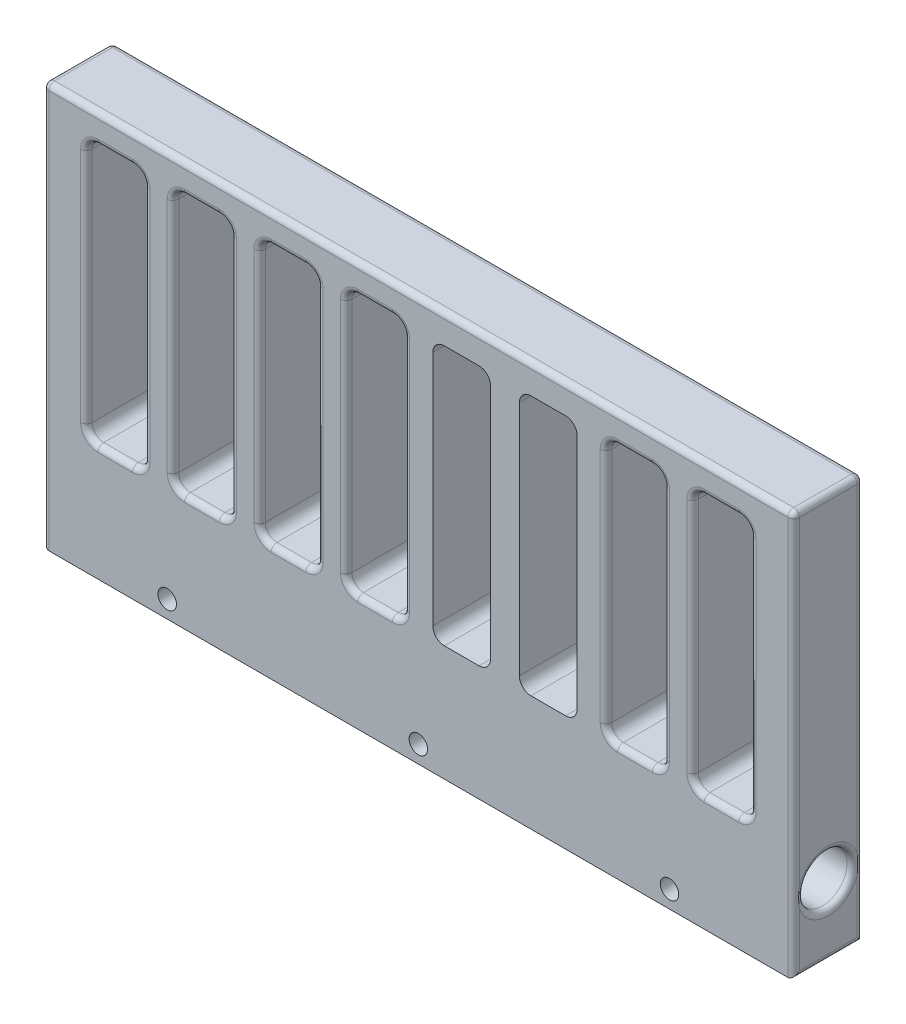
SolidWorks part; units mm, degrees
ref_plane "Plan de face" through (0, 0, 0) normal (0, 0, 1) x (1, 0, 0)
ref_plane "Plan de dessus" through (0, 0, 0) normal (0, 1, 0) x (1, 0, 0)
ref_plane "Plan de droite" through (0, 0, 0) normal (1, 0, 0) x (0, 0, -1)
sketch "Esquisse1" plane through (0, 0, 0) normal (0, 0, 1) x (1, 0, 0)
  line L1 (0, 0) -> (130, 0)
  line L2 (0, 0) -> (0, 70)
  line L3 (0, 70) -> (130, 70)
  line L4 (130, 0) -> (130, 70)
  dimension "D1" = 70
  dimension "D2" = 130
extrude "Boss.-Extru.1" add sketch "Esquisse1" along normal blind 12
sketch "Esquisse2" plane through (0, 0, 12) normal (0, 0, 1) x (1, 0, 0)
  line L31 (0, 20) -> (130, 20) construction
  line L37 (0, 70) -> (0, 0) construction
  line L42 (130, 0) -> (130, 70) construction
  line L47 (0, 0) -> (130, 0) construction
  line L52 (130, 70) -> (0, 70) construction
  line L57 (7.5, 20) -> (17.5, 20)
  line L58 (7.5, 20) -> (7.5, 65)
  line L59 (7.5, 65) -> (17.5, 65)
  line L60 (17.5, 20) -> (17.5, 65)
  line L61 (22.5, 20) -> (22.5, 65)
  line L62 (22.5, 65) -> (32.5, 65)
  line L63 (32.5, 20) -> (32.5, 65)
  line L64 (22.5, 20) -> (32.5, 20)
  line L65 (37.5, 20) -> (37.5, 65)
  line L66 (37.5, 65) -> (47.5, 65)
  line L67 (47.5, 20) -> (47.5, 65)
  line L68 (37.5, 20) -> (47.5, 20)
  line L69 (52.5, 20) -> (52.5, 65)
  line L70 (52.5, 65) -> (62.5, 65)
  line L71 (62.5, 20) -> (62.5, 65)
  line L72 (52.5, 20) -> (62.5, 20)
  line L73 (67.5, 20) -> (67.5, 65)
  line L74 (67.5, 65) -> (77.5, 65)
  line L75 (77.5, 20) -> (77.5, 65)
  line L76 (67.5, 20) -> (77.5, 20)
  line L77 (82.5, 20) -> (82.5, 65)
  line L78 (82.5, 65) -> (92.5, 65)
  line L79 (92.5, 20) -> (92.5, 65)
  line L80 (82.5, 20) -> (92.5, 20)
  line L81 (97.5, 20) -> (97.5, 65)
  line L82 (97.5, 65) -> (107.5, 65)
  line L83 (107.5, 20) -> (107.5, 65)
  line L84 (97.5, 20) -> (107.5, 20)
  line L85 (112.5, 20) -> (112.5, 65)
  line L86 (112.5, 65) -> (122.5, 65)
  line L87 (122.5, 20) -> (122.5, 65)
  line L88 (112.5, 20) -> (122.5, 20)
  dimension "D5" = 8
  dimension "D1" = 20
  dimension "D2" = 10
  dimension "D3" = 5
  dimension "D4" = 7.5
extrude "Enlèv. mat.-Extru.2" cut sketch "Esquisse2" against normal blind 12
sketch "Esquisse3" plane through (0, 0, 0) normal (-1, 0, 0) x (0, 0, 1)
  line L0 (6, 0) -> (6, 16.1007) construction
  line L1 (12, 0) -> (0, 0) construction
  line L2 (6, 7.75) -> (6, 0) construction
  circle A0 centre (6, 12) radius 4.25
  dimension "D1" = 8.5
  dimension "D2" = 12
extrude "Enlèv. mat.-Extru.3" cut sketch "Esquisse3" against normal blind 154
sketch "Esquisse4" plane through (0, 0, 12) normal (0, 0, 1) x (1, 0, 0)
  line L0 (0, 3) -> (130, 3) construction
  line L1 (0, 70) -> (0, 0) construction
  line L2 (130, 0) -> (130, 70) construction
  line L3 (0, 0) -> (130, 0) construction
  circle A0 centre (21.5, 3) radius 1.6
  circle A1 centre (65, 3) radius 1.6
  circle A2 centre (108.5, 3) radius 1.6
  dimension "D2" = 3.2
  dimension "D3" = 3.2
  dimension "D4" = 3.2
  dimension "D5" = 21.5
  dimension "D6" = 21.5
  dimension "D1" = 3
extrude "Enlèv. mat.-Extru.4" cut sketch "Esquisse4" against normal blind 16
sketch "Esquisse6" plane through (0, 0, 0) normal (0, 0, -1) x (-1, 0, 0)
  line L1 (-20.1634, 5.6237) -> (-23.1039, 5.4693)
  line L2 (-23.1039, 5.4693) -> (-24.4404, 2.8457)
  line L3 (-24.4404, 2.8457) -> (-22.8366, 0.3763)
  line L4 (-22.8366, 0.3763) -> (-19.8961, 0.5307)
  line L5 (-19.8961, 0.5307) -> (-18.5596, 3.1543)
  line L6 (-18.5596, 3.1543) -> (-20.1634, 5.6237)
  line L7 (-62.4628, 4.4942) -> (-65.0254, 5.9444)
  line L8 (-65.0254, 5.9444) -> (-67.5626, 4.4502)
  line L9 (-67.5626, 4.4502) -> (-67.5372, 1.5058)
  line L10 (-67.5372, 1.5058) -> (-64.9746, 0.0556)
  line L11 (-64.9746, 0.0556) -> (-62.4374, 1.5498)
  line L12 (-62.4374, 1.5498) -> (-62.4628, 4.4942)
  line L13 (-106.0063, 4.5658) -> (-108.6091, 5.9425)
  line L14 (-108.6091, 5.9425) -> (-111.1028, 4.3767)
  line L15 (-111.1028, 4.3767) -> (-110.9937, 1.4342)
  line L16 (-110.9937, 1.4342) -> (-108.3909, 0.0575)
  line L17 (-108.3909, 0.0575) -> (-105.8972, 1.6233)
  line L18 (-105.8972, 1.6233) -> (-106.0063, 4.5658)
  circle A0 centre (-21.5, 3) radius 2.55 construction
  circle A1 centre (-65, 3) radius 2.55 construction
  circle A2 centre (-108.5, 3) radius 2.55 construction
  dimension "D1" = 5.1
  dimension "D2" = 5.1
  dimension "D3" = 5.1
extrude "Enlèv. mat.-Extru.5" cut sketch "Esquisse6" against normal blind 3
fillet "Congé1" radius 2 32 edges at (67.5, 20, 6) (52.5, 20, 6) (37.5, 20, 6) (22.5, 20, 6) (7.5, 20, 6) (82.5, 20, 6) (97.5, 20, 6) (7.5, 65, 6) (22.5, 65, 6) (37.5, 65, 6) (52.5, 65, 6) (67.5, 65, 6) (82.5, 65, 6) (97.5, 65, 6) (112.5, 65, 6) (122.5, 65, 6) (107.5, 65, 6) (92.5, 65, 6) (77.5, 65, 6) (62.5, 65, 6) (47.5, 65, 6) (32.5, 65, 6) (17.5, 65, 6) (17.5, 20, 6) (32.5, 20, 6) (47.5, 20, 6) (62.5, 20, 6) (77.5, 20, 6) (92.5, 20, 6) (107.5, 20, 6) (122.5, 20, 6) (112.5, 20, 6)
fillet "Congé2" radius 1 116 edges at (8.0858, 64.4142, 0) (12.5, 65, 0) (16.9142, 64.4142, 0) (17.5, 42.5, 0) (16.9142, 20.5858, 0) (12.5, 20, 0) (8.0858, 20.5858, 0) (8.0858, 64.4142, 12) (12.5, 65, 12) (16.9142, 64.4142, 12) (17.5, 42.5, 12) (16.9142, 20.5858, 12) (12.5, 20, 12) (8.0858, 20.5858, 12) (23.0858, 64.4142, 0) (27.5, 65, 0) (31.9142, 64.4142, 0) (32.5, 42.5, 0) (31.9142, 20.5858, 0) (27.5, 20, 0) (23.0858, 20.5858, 0) (23.0858, 64.4142, 12) (27.5, 65, 12) (31.9142, 64.4142, 12) (32.5, 42.5, 12) (31.9142, 20.5858, 12) (27.5, 20, 12) (23.0858, 20.5858, 12) (38.0858, 64.4142, 0) (42.5, 65, 0) (46.9142, 64.4142, 0) (47.5, 42.5, 0) (46.9142, 20.5858, 0) (42.5, 20, 0) (38.0858, 20.5858, 0) (38.0858, 64.4142, 12) (42.5, 65, 12) (46.9142, 64.4142, 12) (47.5, 42.5, 12) (46.9142, 20.5858, 12) (42.5, 20, 12) (38.0858, 20.5858, 12) (53.0858, 64.4142, 12) (57.5, 65, 12) (61.9142, 64.4142, 12) (62.5, 42.5, 12) (61.9142, 20.5858, 12) (57.5, 20, 12) (53.0858, 20.5858, 12) (98.0858, 64.4142, 0) (102.5, 65, 0) (106.9142, 64.4142, 0) (107.5, 42.5, 0) (106.9142, 20.5858, 0) (102.5, 20, 0) (98.0858, 20.5858, 0) (98.0858, 64.4142, 12) (102.5, 65, 12) (106.9142, 64.4142, 12) (107.5, 42.5, 12) (106.9142, 20.5858, 12) (102.5, 20, 12) (98.0858, 20.5858, 12) (113.0858, 64.4142, 12) (117.5, 65, 12) (121.9142, 64.4142, 12) (122.5, 42.5, 12) (121.9142, 20.5858, 12) (117.5, 20, 12) (113.0858, 20.5858, 12) (113.0858, 64.4142, 0) (117.5, 65, 0) (121.9142, 64.4142, 0) (122.5, 42.5, 0) (121.9142, 20.5858, 0) (117.5, 20, 0) (113.0858, 20.5858, 0) (61.9142, 20.5858, 0) (57.5, 20, 0) (53.0858, 20.5858, 0) (53.0858, 64.4142, 0) (57.5, 65, 0) (61.9142, 64.4142, 0) (76.9142, 20.5858, 0) (72.5, 20, 0) (68.0858, 20.5858, 0) (67.5, 42.5, 0) (68.0858, 64.4142, 0) (72.5, 65, 0) (76.9142, 64.4142, 0) (0, 35, 12) (0, 0, 6) (0, 35, 0) (0, 12, 10.25) (130, 0, 6) (130, 35, 12) (130, 35, 0) (130, 12, 10.25) (7.5, 42.5, 0) (7.5, 42.5, 12) (22.5, 42.5, 0) (22.5, 42.5, 12) (37.5, 42.5, 0) (37.5, 42.5, 12) (52.5, 42.5, 0) (52.5, 42.5, 12) (97.5, 42.5, 0) (97.5, 42.5, 12) (112.5, 42.5, 12) (112.5, 42.5, 0) (130, 70, 6) (65, 70, 12) (0, 70, 6) (65, 70, 0) (62.5, 42.5, 0) (77.5, 42.5, 0)
